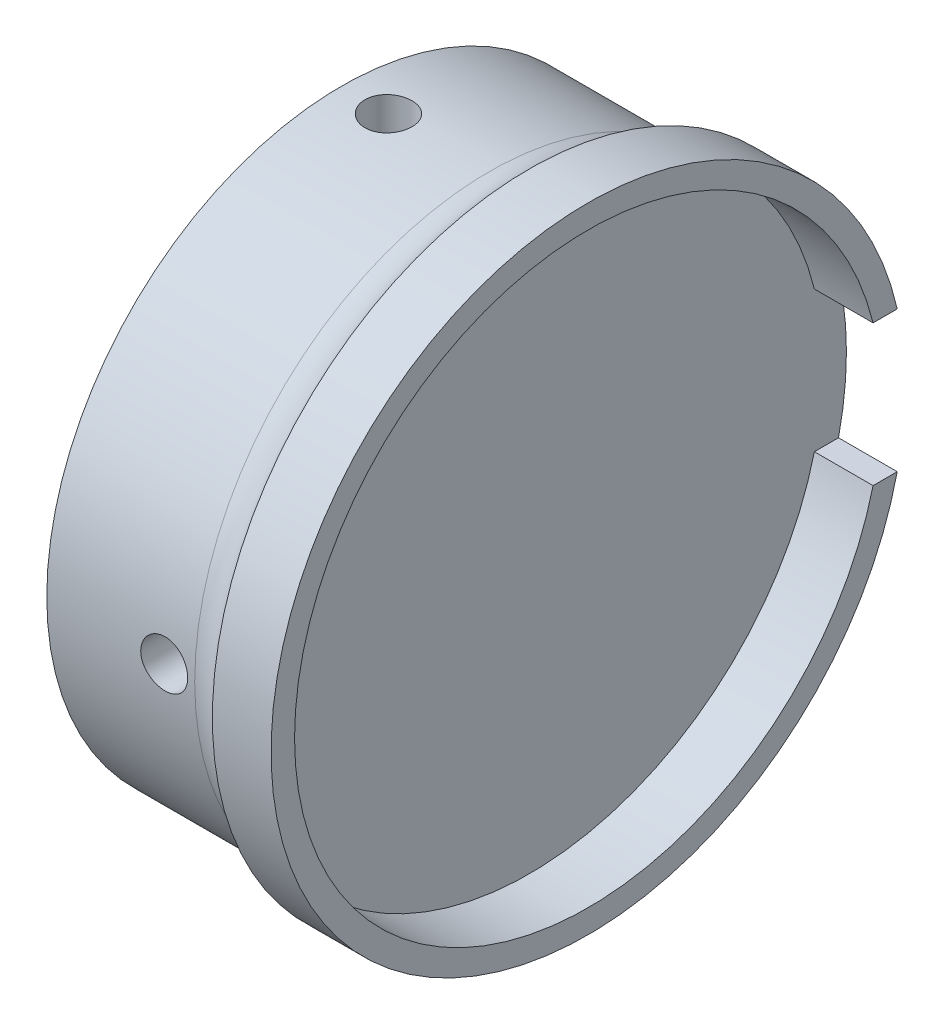
SolidWorks part; units mm, degrees
ref_plane "前视基准面" through (0, 0, 0) normal (0, 0, 1) x (1, 0, 0)
ref_plane "上视基准面" through (0, 0, 0) normal (0, 1, 0) x (1, 0, 0)
ref_plane "右视基准面" through (0, 0, 0) normal (1, 0, 0) x (0, 0, -1)
other "Configuration Table"
sketch "草图1" plane through (0, 0, 0) normal (1, 0, 0) x (0, 0, -1)
  circle A0 centre (0, 0) radius 12.55
  dimension "D1" = 25.1
extrude "凸台-拉伸1" add sketch "草图1" along normal blind 8
sketch "草图2" plane through (0, 0, 0) normal (-1, 0, 0) x (0, 0, 1)
  circle A0 centre (0, 0) radius 3
  dimension "D1" = 6
extrude "切除-拉伸1" cut sketch "草图2" against normal blind 7
sketch "草图3" plane through (0, 0, 0) normal (0, 1, 0) x (1, 0, 0)
  line L0 (0, 12.55) -> (0, -12.55) construction
  circle A0 centre (2, 0) radius 1
  dimension "D1" = 2
  dimension "D2" = 2
extrude "切除-拉伸2" cut sketch "草图3" against normal up to next and the other way up to next
sketch "草图4" plane through (0, 0, 0) normal (0, 0, 1) x (1, 0, 0)
  line L1 (0, 12.55) -> (0, -12.55) construction
  circle A0 centre (5, 0) radius 1
  dimension "D2" = 2
  dimension "D1" = 5
extrude "切除-拉伸3" cut sketch "草图4" against normal blind 19 and the other way blind 21
sketch "草图5" plane through (8, 0, 0) normal (1, 0, 0) x (0, 0, -1)
  circle A0 centre (0, 0) radius 13.5
  dimension "D1" = 27
extrude "凸台-拉伸2" add sketch "草图5" along normal blind 2.5
sketch "草图6" plane through (10.5, 0, 0) normal (1, 0, 0) x (0, 0, -1)
  circle A0 centre (0, 0) radius 12.5
  dimension "D1" = 25
extrude "切除-拉伸4" cut sketch "草图6" against normal blind 2.5
fillet "圆角1" radius 2 1 edges at (8, 0, -12.55)
sketch "草图7" plane through (0, 0, 0) normal (0, 0, 1) x (1, 0, 0)
  line L0 (0, 0) -> (10.5, 0) construction
  line L1 (10.5, -13.5) -> (10.5, 13.5) construction
  line L2 (8, 13.5) -> (8, -13.5) construction
  line L3 (8, 3) -> (10.5, 3)
  line L4 (8, 3) -> (8, -3)
  line L5 (8, -3) -> (10.5, -3)
  line L6 (10.5, 3) -> (10.5, -3)
  dimension "D1" = 6
  dimension "D2" = 3
extrude "切除-拉伸5" cut sketch "草图7" against normal blind 21.5
